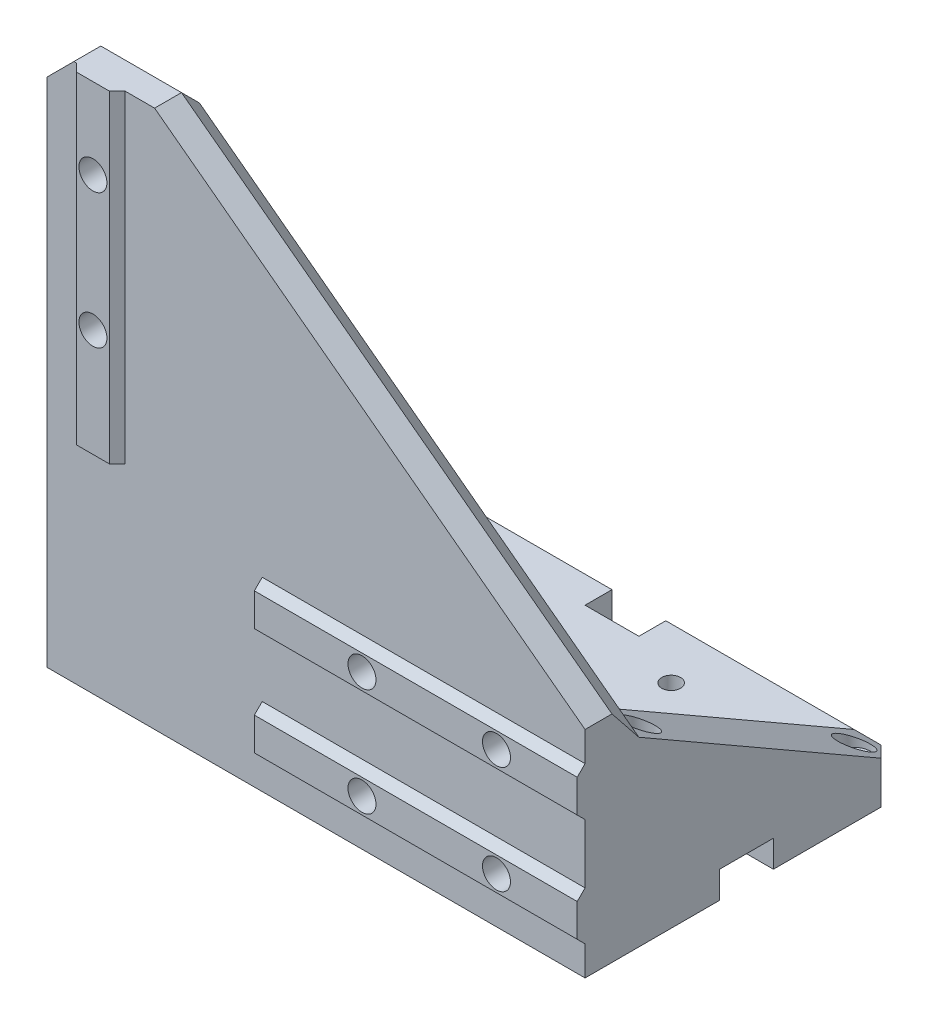
SolidWorks part; units mm, degrees
ref_plane "Płaszczyzna przednia" through (0, 0, 0) normal (0, 0, 1) x (1, 0, 0)
ref_plane "Płaszczyzna górna" through (0, 0, 0) normal (0, 1, 0) x (1, 0, 0)
ref_plane "Płaszczyzna prawa" through (0, 0, 0) normal (1, 0, 0) x (0, 0, -1)
sketch "Sketch1" plane through (0, 0, 0) normal (0, 0, 1) x (1, 0, 0)
  line L0 (0, 0) -> (100, 0)
  line L1 (100, 0) -> (100, 40)
  line L2 (100, 40) -> (20, 100)
  line L3 (20, 100) -> (0, 100)
  line L4 (0, 100) -> (0, 0)
  line L5 (10, 100) -> (10, 0) construction
  line L6 (30, 100) -> (30, 0) construction
  line L8 (100, 30) -> (0, 30) construction
  dimension "D1" = 20
  dimension "D2" = 40
  dimension "D3" = 100
extrude "Boss-Extrude1" add sketch "Sketch1" along normal blind 10
sketch "Sketch2" plane through (0, 0, 0) normal (0, 0, 1) x (1, 0, 0)
  line L5 (10, 100) -> (10, 0) construction
  line L7 (100, 10) -> (0, 10) construction
  line L8 (100, 30) -> (0, 30) construction
  line L9 (0, 0) -> (100, 0) construction
  line L10 (0, 100) -> (0, 0) construction
  line L11 (100, 0) -> (100, 40) construction
  line L12 (0, 100) -> (0, 0) construction
  line L13 (20, 100) -> (0, 100) construction
  line L14 (0, 0) -> (100, 0) construction
  circle A0 centre (10, 85) radius 2.6
  circle A2 centre (10, 60) radius 2.6
  circle A4 centre (85, 30) radius 2.6
  circle A5 centre (85, 10) radius 2.6
  circle A6 centre (60, 10) radius 2.6
  circle A7 centre (60, 30) radius 2.6
  dimension "D9" = 60
  dimension "D1" = 10
  dimension "D2" = 10
  dimension "D4" = 15
  dimension "D6" = 60
  dimension "D7" = 15
  dimension "D8" = 20
extrude "Cut-Extrude1" cut sketch "Sketch2" along normal through all
sketch "Sketch3" plane through (0, 0, 0) normal (0, 0, 1) x (1, 0, 0)
  line L0 (0, 100) -> (0, 0) construction
  line L1 (100, 0) -> (100, 40) construction
  line L2 (100, 25.5) -> (40, 25.5)
  line L3 (100, 25.5) -> (100, 34.5)
  line L4 (100, 34.5) -> (40, 34.5)
  line L5 (40, 25.5) -> (40, 34.5)
  line L6 (20, 100) -> (0, 100) construction
  line L7 (100, 5.5) -> (40, 5.5)
  line L8 (100, 5.5) -> (100, 14.5)
  line L9 (100, 14.5) -> (40, 14.5)
  line L10 (40, 5.5) -> (40, 14.5)
  line L11 (14.5, 100) -> (5.5, 100)
  line L12 (14.5, 100) -> (14.5, 40)
  line L13 (14.5, 40) -> (5.5, 40)
  line L14 (5.5, 100) -> (5.5, 40)
  line L15 (0, 0) -> (100, 0) construction
  circle A0 centre (60, 30) radius 2.6 construction
  circle A1 centre (60, 10) radius 2.6 construction
  circle A3 centre (10, 60) radius 2.6 construction
  dimension "D3" = 4.5
  dimension "D6" = 4.5
  dimension "D10" = 4.5
  dimension "D1" = 40
  dimension "D2" = 40
  dimension "D4" = 9
  dimension "D5" = 9
  dimension "D8" = 9
  dimension "D11" = 40
extrude "Boss-Extrude3" add sketch "Sketch3" along normal blind 1.46 from surface starting at face at (12.6, 85, 10)
extrude "Cut-Extrude2" cut sketch "Sketch2<2>" along normal through all both and the other way through all
sketch "Sketch2<2>" plane through (0, 0, 0) normal (0, 0, 1) x (1, 0, 0) same geometry as "Sketch2"
chamfer "Chamfer1" distance 1.46 angle 45 6 edges at (14.5, 70, 11.46) (5.5, 70, 11.46) (70, 5.5, 11.46) (70, 14.5, 11.46) (70, 25.5, 11.46) (70, 34.5, 11.46)
sketch "Sketch4" plane through (0, 0, 0) normal (0, 0, 1) x (1, 0, 0)
  circle A0 centre (10, 85) radius 4.5
  circle A3 centre (10, 60) radius 4.5
  circle A4 centre (60, 30) radius 4.5
  circle A5 centre (85, 30) radius 4.5
  circle A6 centre (85, 10) radius 4.5
  circle A7 centre (60, 10) radius 4.5
  dimension "D1" = 9
extrude "Cut-Extrude3" cut sketch "Sketch4" along normal blind 5 from surface starting at face at (12.6, 85, 0)
sketch "Sketch5" plane through (0, 0, 0) normal (0, 1, 0) x (1, 0, 0)
  line L0 (100, 25) -> (0, 25) construction
  line L1 (100, 0) -> (0, 0)
  line L2 (100, 0) -> (100, 50)
  line L3 (100, 50) -> (0, 50)
  line L4 (0, 0) -> (0, 50)
  line L5 (50, 50) -> (50, 0) construction
  line L7 (0, -10) -> (0, 0) construction
  line L8 (65.5, 40.5) -> (34.5, 40.5) construction
  line L9 (65.5, 40.5) -> (65.5, 9.5) construction
  line L10 (65.5, 9.5) -> (34.5, 9.5) construction
  line L11 (34.5, 40.5) -> (34.5, 9.5) construction
  line L12 (65.5, 40.5) -> (34.5, 9.5) construction
  line L13 (65.5, 9.5) -> (34.5, 40.5) construction
  line L14 (100, -10) -> (100, 0) construction
  circle A0 centre (50, 25) radius 11.5
  circle A1 centre (65.5, 9.5) radius 1.75
  circle A2 centre (34.5, 9.5) radius 1.75
  circle A3 centre (34.5, 40.5) radius 1.75
  circle A4 centre (65.5, 40.5) radius 1.75
  dimension "D2" = 23
  dimension "D5" = 3.5
  dimension "D1" = 50
  dimension "D3" = 31
  dimension "D4" = 31
extrude "Boss-Extrude4" add sketch "Sketch5" along normal blind 5
sketch "Sketch8" plane through (0, 0, 0) normal (1, 0, 0) x (0, 0, -1)
  line L0 (0, 5) -> (50, 5)
  line L1 (50, 5) -> (0, 33.75)
  line L2 (0, 33.75) -> (0, 5)
  point P4 (0, 0)
  point P7 (0, 0)
  point P8 (0, 0)
  dimension "D1" = 28.75
extrude "Boss-Extrude5" add sketch "Sketch8" along normal blind 10
extrude "Boss-Extrude6" add sketch "Sketch8<2>" against normal blind 10 from surface starting at face at (100, 17.8571, 0.4171)
sketch "Sketch8<2>" plane through (0, 0, 0) normal (1, 0, 0) x (0, 0, -1) same geometry as "Sketch8"
sketch "Sketch9" plane through (0, 0, 0) normal (0, 1, 0) x (1, 0, 0)
  line L0 (95, 5) -> (5, 5) construction
  line L1 (95, 5) -> (95, 45) construction
  line L2 (5, 5) -> (5, 45) construction
  line L3 (95, 45) -> (5, 45) construction
  line L4 (0, -10) -> (100, -10) construction
  line L5 (100, 50) -> (0, 50) construction
  line L6 (0, -10) -> (0, 50) construction
  line L7 (100, -10) -> (100, 50) construction
  circle A0 centre (95, 45) radius 1.75
  circle A1 centre (5, 45) radius 1.75
  circle A2 centre (5, 5) radius 1.75
  circle A3 centre (95, 5) radius 1.75
  dimension "D5" = 3.5
  dimension "D1" = 15
  dimension "D2" = 5
  dimension "D3" = 5
  dimension "D4" = 5
extrude "Cut-Extrude4" cut sketch "Sketch9" along normal through all both and the other way through all
sketch "Sketch11" plane through (0, 0, 0) normal (0, 1, 0) x (1, 0, 0)
  circle A0 centre (95, 5) radius 3
  circle A1 centre (95, 45) radius 3
  circle A2 centre (5, 5) radius 3
  circle A3 centre (5, 45) radius 3
  dimension "D1" = 6
extrude "Cut-Extrude5" cut sketch "Sketch11" against normal blind 95 from surface starting at face at (10, 100, 7.865)
sketch "Sketch12" plane through (0, 0, 0) normal (0, 1, 0) x (1, 0, 0)
  line L0 (100, 25) -> (100, 15)
  line L1 (100, 25) -> (95, 25)
  line L2 (100, 15) -> (95, 15)
  line L3 (95, 25) -> (95, 15)
  line L4 (100, -10) -> (100, 50) construction
  line L5 (100, 50) -> (0, 50) construction
  line L6 (0, 25) -> (0, 15)
  line L7 (0, 25) -> (5, 25)
  line L8 (0, 15) -> (5, 15)
  line L9 (5, 25) -> (5, 15)
  line L10 (0, -10) -> (0, 50) construction
  line L11 (45, 50) -> (55, 50)
  line L12 (45, 50) -> (45, 45)
  line L13 (55, 50) -> (55, 45)
  line L14 (45, 45) -> (55, 45)
  dimension "D1" = 25
  dimension "D2" = 10
  dimension "D3" = 5
  dimension "D4" = 5
  dimension "D5" = 10
  dimension "D6" = 45
extrude "Cut-Extrude6" cut sketch "Sketch12" along normal blind 5
chamfer "Chamfer2" distance 5 angle 45 6 edges at (100, 2.5, -50) (0, 2.5, -50) (60, 70, 0) (0, 100, 5) (10, 100, 0) (0, 66.875, 0)
